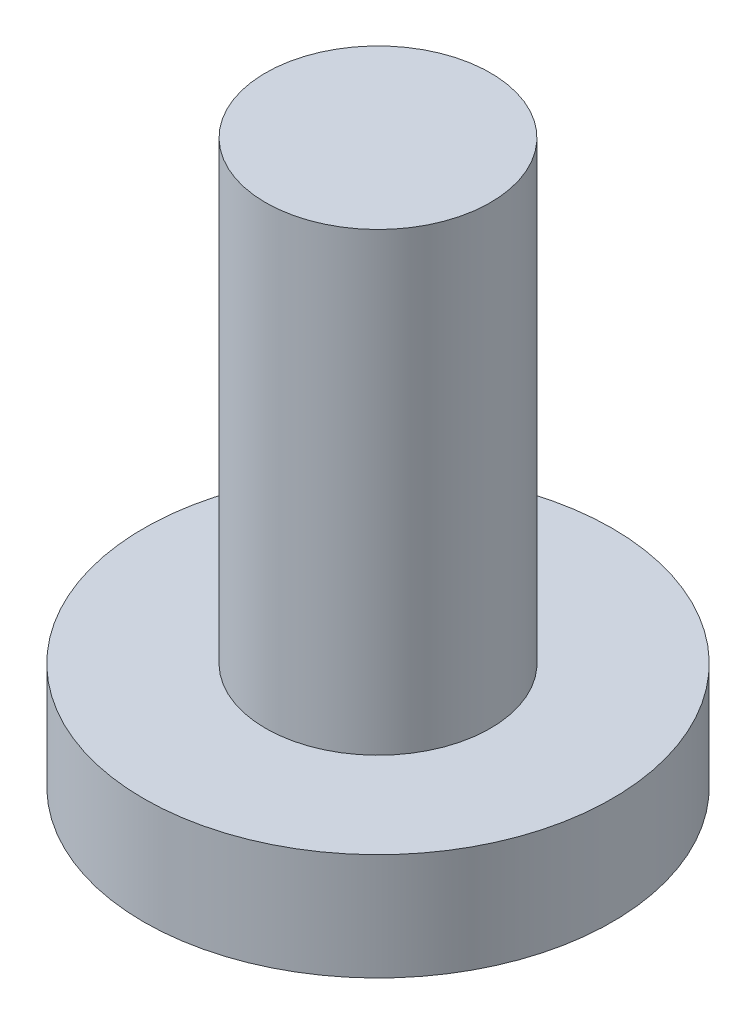
SolidWorks part; units mm, degrees
ref_plane "Front Plane" through (0, 0, 0) normal (0, 0, 1) x (1, 0, 0)
ref_plane "Top Plane" through (0, 0, 0) normal (0, 1, 0) x (1, 0, 0)
ref_plane "Right Plane" through (0, 0, 0) normal (1, 0, 0) x (0, 0, -1)
sketch "Sketch1" plane through (0, 0, 0) normal (0, 1, 0) x (1, 0, 0)
  circle A0 centre (0, 0) radius 7.5
  circle A1 centre (0, 0) radius 3.6
  dimension "D1" = 7.2
  dimension "D2" = 15
extrude "Boss-Extrude1" add sketch "Sketch1" along normal blind 3.42
extrude "Boss-Extrude2" add sketch "Sketch1<2>" along normal blind 18 contours A1 region at (0, 0, 0)
sketch "Sketch1<2>" plane through (0, 0, 0) normal (0, 1, 0) x (1, 0, 0) same geometry as "Sketch1"
